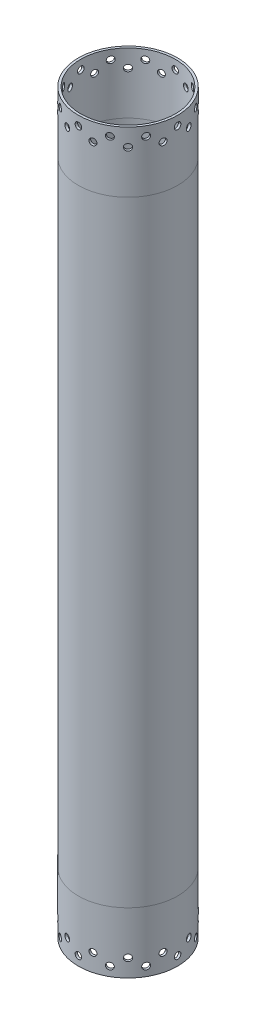
SolidWorks part; units mm, degrees
material "6061-T6 (SS)"
ref_plane "Front Plane" through (0, 0, 0) normal (0, 0, 1) x (1, 0, 0)
ref_plane "Top Plane" through (0, 0, 0) normal (0, 1, 0) x (1, 0, 0)
ref_plane "Right Plane" through (0, 0, 0) normal (1, 0, 0) x (0, 0, -1)
sketch "Sketch2" plane through (0, 0, 0) normal (0, 1, 0) x (1, 0, 0)
  circle A0 centre (0, 0) radius 76.2
  circle A1 centre (0, 0) radius 72.5932
  dimension "D1" = 152.4
  dimension "D2" = 145.1864
extrude "Boss-Extrude1" add sketch "Sketch2" along normal blind 1130.3
sketch "Sketch3" plane through (0, 0, 0) normal (0, 0, 1) x (1, 0, 0)
  line L0 (0, 1130.3) -> (0, 1116.203) construction
  line L1 (72.5932, 1130.3) -> (-72.5932, 1130.3) construction
  circle A0 centre (0, 1116.203) radius 5.0419
  dimension "D1" = 10.0838
  dimension "D2" = 14.097
extrude "Cut-Extrude1" cut sketch "Sketch3" against normal blind 1143
ref_plane "Plane1" through (-19.722, 0, 73.6035) normal (-0.2588, 0, 0.9659) x (0, -1, 0)
sketch "Sketch6" plane through (-19.722, 0, 73.6035) normal (-0.2588, 0, 0.9659) x (0, -1, 0)
  line L0 (-1130.3, 0) -> (-1103.503, 0) construction
  line L1 (-1130.3, 76.2) -> (-1130.3, -76.2) construction
  circle A0 centre (-1103.503, 0) radius 5.0419
  dimension "D1" = 10.0838
  dimension "D2" = 26.797
extrude "Cut-Extrude2" cut sketch "Sketch6" against normal blind 25.4
pattern_circular "CirPattern2" count 12 over 360 about axis through (0, 1130.3, 0) along (0, -1, 0) of "Cut-Extrude2", "Cut-Extrude1"
ref_plane "Plane2" through (0, 565.15, 0) normal (0, 1, 0) x (1, 0, 0)
mirror "Mirror1" about plane through (0, 565.15, 0) normal (0, 1, 0) of "CirPattern2"
ref_plane "Plane3" through (0, 93.218, 0) normal (0, -1, 0) x (-1, 0, 0)
ref_plane "Plane4" through (0, 1037.082, 0) normal (0, 1, 0) x (1, 0, 0)
split line "Split Line1"
split line "Split Line2"
ref_axis "Axis1" through (-52.4853, 1103.503, 52.4853) along (-0.7071, 0, 0.7071)
ref_axis "Axis2" through (-18.7541, 1103.503, 69.9914) along (-0.2588, 0, 0.9659)
ref_plane "Plane5" through (0, 1103.503, 0) normal (0, -1, 0) x (-1, 0, 0)
ref_axis "Axis3" through (-37.6178, 1116.203, 65.1559) along (0.5, 0, -0.866)
ref_axis "Axis4" through (-65.1541, 1116.203, 37.6168) along (0.866, 0, -0.5)
ref_plane "Plane6" through (0, 1116.203, 0) normal (0, 1, 0) x (1, 0, 0)
ref_axis "Axis5" through (-37.6178, 14.097, 65.1559) along (0.5, 0, -0.866)
ref_axis "Axis6" through (0, 14.097, 76.2) along (0, 0, -1)
ref_axis "Axis7" through (-18.7541, 26.797, 69.9914) along (-0.2588, 0, 0.9659)
ref_axis "Axis8" through (-52.4853, 26.797, 52.4853) along (-0.7071, 0, 0.7071)
ref_plane "Plane7" through (0, 26.797, 0) normal (0, 1, 0) x (1, 0, 0)
ref_plane "Plane8" through (0, 14.097, 0) normal (0, 1, 0) x (1, 0, 0)
split line "Split Line3"
split line "Split Line4"
split line "Split Line5"
split line "Split Line6"
equation "\"holeDia\"=0.397"
equation "\"D1@Sketch3\"=\"holeDia\""
equation "\"D1@Sketch6\"=\"holeDia\""
equation "\"numHoles\"=12"
equation "\"D1@CirPattern2\"=\"numHoles\""
equation "\"D1@Plane1\"=180/\"numHoles\""
equation "\"D2@Sketch6\"=\"D2@Sketch3\"+0.5"
